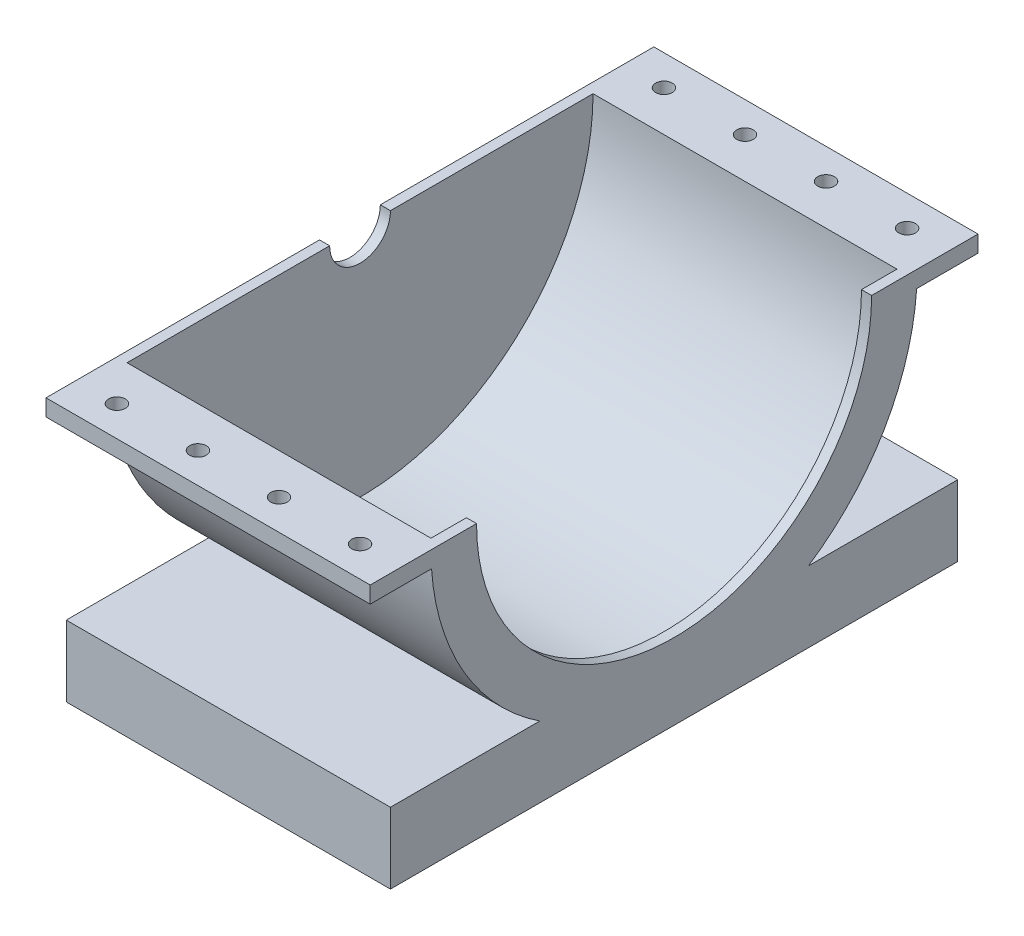
SolidWorks part; units mm, degrees
ref_plane "Front Plane" through (0, 0, 0) normal (0, 0, 1) x (1, 0, 0)
ref_plane "Top Plane" through (0, 0, 0) normal (0, 1, 0) x (1, 0, 0)
ref_plane "Right Plane" through (0, 0, 0) normal (1, 0, 0) x (0, 0, -1)
sketch "Sketch1" plane through (0, 0, 0) normal (1, 0, 0) x (0, 0, -1)
  line L0 (0, 0) -> (0, 1887.1899) construction
  line L1 (0, 0) -> (1887.1899, 0) construction
  line L3 (-7, -0.875) -> (7, -0.875)
  line L4 (-7, -0.875) -> (-7, 0.875)
  line L5 (-7, 0.875) -> (7, 0.875)
  line L6 (7, -0.875) -> (7, 0.875)
  line L7 (-7, -0.875) -> (7, 0.875) construction
  line L8 (-7, 0.875) -> (7, -0.875) construction
  line L9 (-7.5, 5.875) -> (7.5, 5.875)
  line L10 (-7.5, 5.875) -> (-7.5, 5.465)
  line L11 (-7.5, 5.465) -> (7.5, 5.465)
  line L12 (7.5, 5.875) -> (7.5, 5.465)
  line L13 (-7.5, 5.875) -> (7.5, 5.465) construction
  line L14 (-7.5, 5.465) -> (7.5, 5.875) construction
  arc A0 (6, 5.875) -> (-6, 5.875) centre (0, 5.875) cw
  point P5 (0, 0)
  point P10 (0, 5.67)
  dimension "D6" = 6
  dimension "D1" = 0.41
  dimension "D2" = 14
  dimension "D3" = 6.75
  dimension "D4" = 5
  dimension "D5" = 15
extrude "Boss-Extrude1" add sketch "Sketch1" along normal mid plane 8 contours L5 A0 L4 L3 L6 | A0 L11 L5 | A0 L5 | L9 L12 L11 L10 region at (0, 0, 6.8589) region at (0, 3.3571, 0) region at (0, 0.472, 0)
sketch "Sketch2" plane through (0, 0, 0) normal (1, 0, 0) x (0, 0, -1)
  line L0 (-7.5, 5.875) -> (7.5, 5.875) construction
  circle A0 centre (0, 5.875) radius 5.75
  dimension "D1" = 11.5
extrude "Cut-Extrude1" cut sketch "Sketch2" against normal mid plane 7.5
sketch "Sketch5" plane through (0, 5.875, 0) normal (0, 1, 0) x (1, 0, 0)
  line L0 (-4, -7.5) -> (-4, 7.5) construction
  line L1 (4, 7.5) -> (-4, 7.5) construction
  circle A0 centre (-3, 6.75) radius 0.205
  dimension "D1" = 0.41
  dimension "D2" = 1
  dimension "D3" = 0.75
extrude "Cut-Extrude2" cut sketch "Sketch5" along direction (0, 1, 0) on the side against the normal up to next (0.41 mm away)
pattern_linear "LPattern1" count 4 spacing 2 along (1, 0, 0) count 2 spacing 13.5 along (0, 0, 1) of "Cut-Extrude2"
sketch "Sketch6" plane through (4, 0, 0) normal (1, 0, 0) x (0, 0, -1)
  line L0 (-7.5, 5.875) -> (7.5, 5.875) construction
  circle A0 centre (0, 5.875) radius 0.75
  circle A1 centre (0, 5.875) radius 4.875
  line M5 (7.5, 5.875) -> (-7.5, 5.875)
  dimension "D1" = 1.5
  dimension "D2" = 9.75
extrude "Cut-Extrude3" cut sketch "Sketch6" against normal through all contours A0 M5 region at (4, 5.5567, 0)
extrude "Cut-Extrude4" cut sketch "Sketch6<3>" against normal up to next
sketch "Sketch6<3>" plane through (4, 0, 0) normal (1, 0, 0) x (0, 0, -1) same geometry as "Sketch6"
scale "Scale1" scale about centroid uniform scaling yes scale factor 25.4
